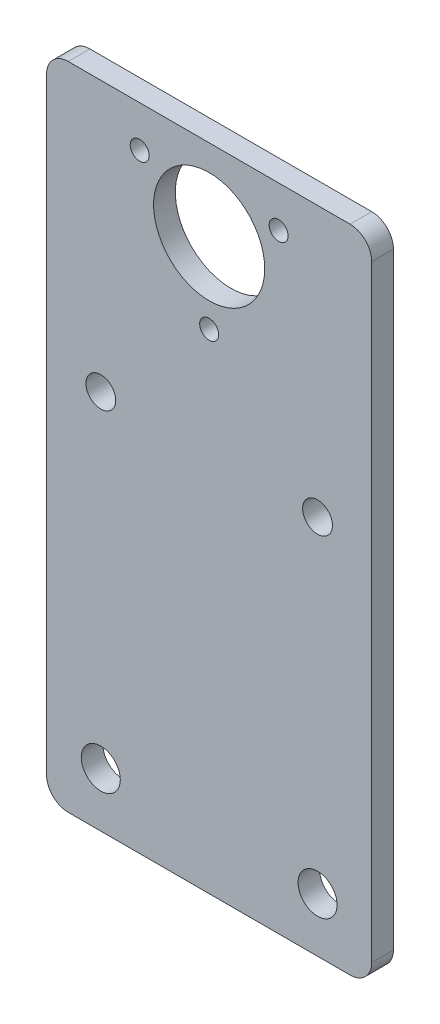
SolidWorks part; units mm, degrees
ref_plane "Płaszczyzna przednia" through (0, 0, 0) normal (0, 0, 1) x (1, 0, 0)
ref_plane "Płaszczyzna górna" through (0, 0, 0) normal (0, 1, 0) x (1, 0, 0)
ref_plane "Płaszczyzna prawa" through (0, 0, 0) normal (1, 0, 0) x (0, 0, -1)
sketch "Szkic1" plane through (0, 0, 0) normal (0, 0, 1) x (1, 0, 0)
  line L0 (19.1159, 65.7063) -> (19.1159, 95.5063) construction
  line L1 (-10.8841, -24.4937) -> (49.1159, -24.4937)
  line L2 (-10.8841, -24.4937) -> (-10.8841, 95.5063)
  line L3 (-10.8841, 95.5063) -> (49.1159, 95.5063)
  line L4 (49.1159, -24.4937) -> (49.1159, 95.5063)
  circle A0 centre (-0.8841, 45.7063) radius 2.75
  circle A1 centre (-0.8841, -14.4937) radius 3.6
  circle A2 centre (39.1159, -14.4937) radius 3.6
  circle A3 centre (39.1159, 45.7063) radius 2.75
  circle A4 centre (19.1159, 80.5063) radius 10.25
  circle A5 centre (6.2988, 87.9063) radius 1.75
  circle A6 centre (31.9331, 87.9063) radius 1.75
  circle A7 centre (19.1159, 65.7063) radius 1.75
  dimension "D11" = 7.2
  dimension "D12" = 5.5
  dimension "D13" = 5.5
  dimension "D14" = 7.2
  dimension "D15" = 3.5
  dimension "D16" = 3.5
  dimension "D17" = 20.5
  dimension "3,5" = 3.5
  dimension "D18" = 14.8
  dimension "D19" = 14.8
  dimension "D20" = 14.8
  dimension "D3" = 60.2
  dimension "D4" = 60.2
  dimension "D5" = 10
  dimension "D6" = 10
  dimension "D7" = 10
  dimension "D8" = 10
  dimension "D9" = 60
  dimension "D10" = 120
  dimension "D21" = 10
  dimension "D22" = 10
  dimension "D23" = 30
  dimension "D24" = 15
extrude "Dodanie-wyciągnięcie1" add sketch "Szkic1" along normal blind 4
fillet "Zaokrąglenie1" radius 4 4 edges at (49.1159, 95.5063, 2) (49.1159, -24.4937, 2) (-10.8841, -24.4937, 2) (-10.8841, 95.5063, 2)
